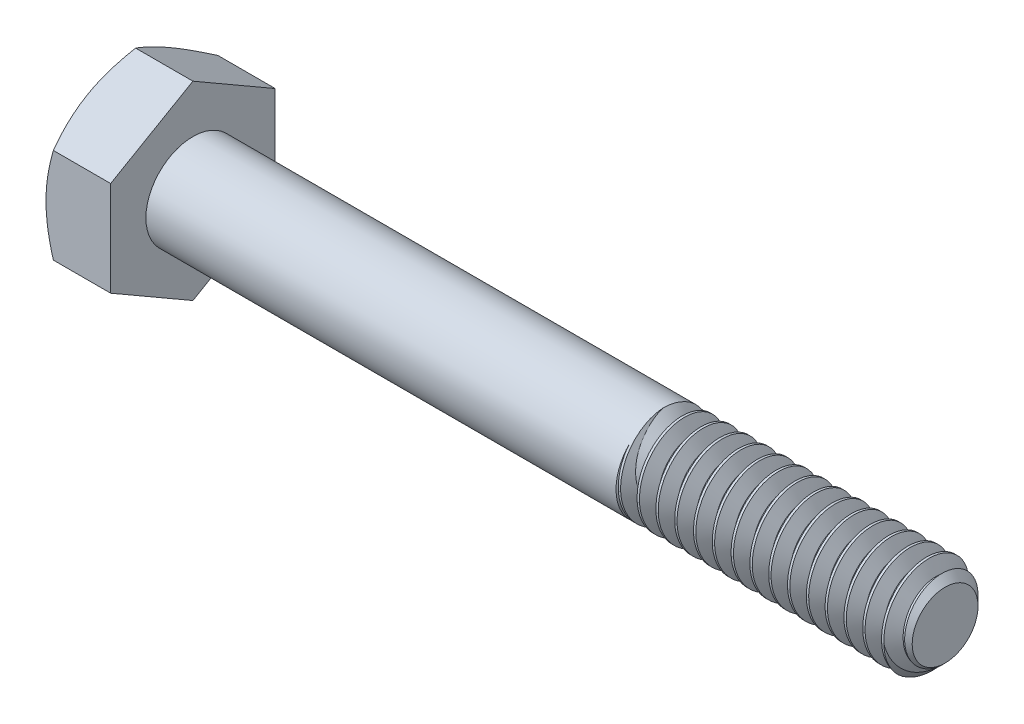
SolidWorks part; units mm, degrees
ref_plane "Front Plane" through (0, 0, 0) normal (0, 0, 1) x (1, 0, 0)
ref_plane "Top Plane" through (0, 0, 0) normal (0, 1, 0) x (1, 0, 0)
ref_plane "Right Plane" through (0, 0, 0) normal (1, 0, 0) x (0, 0, -1)
sketch "Sketch1" plane through (0, 0, 0) normal (0, 0, 1) x (1, 0, 0)
  line L0 (-27.5828, 0) -> (27.5828, 0) construction
  line L1 (27.5828, 3.175) -> (27.5828, -3.175) construction
  line L2 (-23.2172, 5.5562) -> (-23.2172, -5.5562) construction
  line L3 (-27.5828, 5.5562) -> (-27.5828, -5.5562) construction
  point P9 (-23.2172, 0)
  point P10 (23.1378, -3.175)
  dimension "Screw Dia" = 6.35
  dimension "Hex" = 11.1125
  dimension "Head Ht" = 4.3656
  dimension "Screw Lenght" = 50.8
  dimension "D1" = 4.445
ref_plane "Plane2" through (27.5828, 0, 0) normal (1, 0, 0) x (0, 0, -1)
sketch "Sketch5" plane through (27.5828, 0, 0) normal (1, 0, 0) x (0, 0, -1)
  circle A0 centre (0, 0) radius 3.175
extrude "Boss-Extrude3" add sketch "Sketch5" against normal up to vertex (50.8 mm away) up to point (-23.2172, 0, 0)
sketch "Sketch9" plane through (27.5828, 0, 0) normal (1, 0, 0) x (0, 0, -1)
  circle A1 centre (0, 0) radius 3.175
  circle A2 centre (0, 0) radius 3.175
  dimension "D1" = 0
curve "Helix/Spiral1" pitch 1.27 height 20.32 turns 16 parameters "Pitch"=1.27
chamfer "Chamfer1" distance 0.9525 angle 45 1 edges at (27.5828, 0, -3.175)
sketch "Sketch10" plane through (0, 0, 0) normal (0, 0, 1) x (1, 0, 0)
  line L0 (27.5828, 3.175) -> (28.0591, 2.3501)
  line L1 (28.0591, 2.3501) -> (28.2178, 2.3501)
  line L2 (28.2178, 2.3501) -> (28.6941, 3.175)
  line L3 (27.5828, 3.175) -> (28.6941, 3.175)
  line L4 (28.1384, 3.175) -> (28.1384, 2.3501) construction
  line L5 (27.8209, 2.7626) -> (28.4559, 2.7626) construction
  dimension "D1" = 60
  dimension "D2" = 0.1588
  dimension "D3" = 0.635
sweep "Cut-Sweep1" cut profiles "Sketch10" path "Helix/Spiral1" align with end faces yes
sketch "Sketch11" plane through (0, 0, 0) normal (0, 0, 1) x (1, 0, 0)
  line L0 (-23.2172, 3.175) -> (-23.2172, 0)
  line L1 (-23.2172, 0) -> (11.7078, 0)
  line L3 (11.7078, 0) -> (8.5328, 3.175)
  line L4 (-23.2172, 3.175) -> (8.5328, 3.175)
  dimension "D1" = 45
  dimension "MIn Thread" = 19.05
revolve "Revolve1" add sketch "Sketch11" angle 360 about L1
sketch "Sketch6" plane through (-23.2172, 0, 0) normal (-1, 0, 0) x (0, 0, 1)
  line L0 (0, 5.5562) -> (0, -5.5562) construction
  line L1 (5.5563, 3.2079) -> (0, 6.4158)
  line L2 (0, 6.4158) -> (-5.5563, 3.2079)
  line L3 (-5.5563, 3.2079) -> (-5.5563, -3.2079)
  line L4 (-5.5563, -3.2079) -> (0, -6.4158)
  line L5 (0, -6.4158) -> (5.5563, -3.2079)
  line L6 (5.5563, -3.2079) -> (5.5563, 3.2079)
  circle A0 centre (0, 0) radius 5.5562 construction
extrude "Boss-Extrude4" add sketch "Sketch6" along normal up to vertex (4.3656 mm away) up to point (-27.5828, -5.5562, 0)
sketch "Sketch7" plane through (-27.5828, 0, 0) normal (-1, 0, 0) x (0, 0, 1)
  circle A0 centre (0, 0) radius 5.5562 construction
  circle A1 centre (0, 0) radius 5.5562
sketch "Sketch8" plane through (-27.5828, 0, 0) normal (-1, 0, 0) x (0, 0, 1)
  circle A0 centre (0, 0) radius 5.5562 construction
  circle A1 centre (0, 0) radius 5.5562
extrude "Cut-Extrude3" cut sketch "Sketch8" against normal through all draft 60 flip side to cut
equation "\"D2@Sketch10\" = \"Pitch@Helix/Spiral1\"*.125"
equation "\"D3@Sketch10\" = \"Pitch@Helix/Spiral1\"*.5"
equation "\"D3@Helix/Spiral1\" = \"MIn Thread@Sketch11\"+\"Pitch@Helix/Spiral1\""
equation "\"D1@Chamfer1\" = \"Pitch@Helix/Spiral1\"*.75"
equation "\"D1@Sketch1\" = \"Pitch@Helix/Spiral1\"*3.5"
